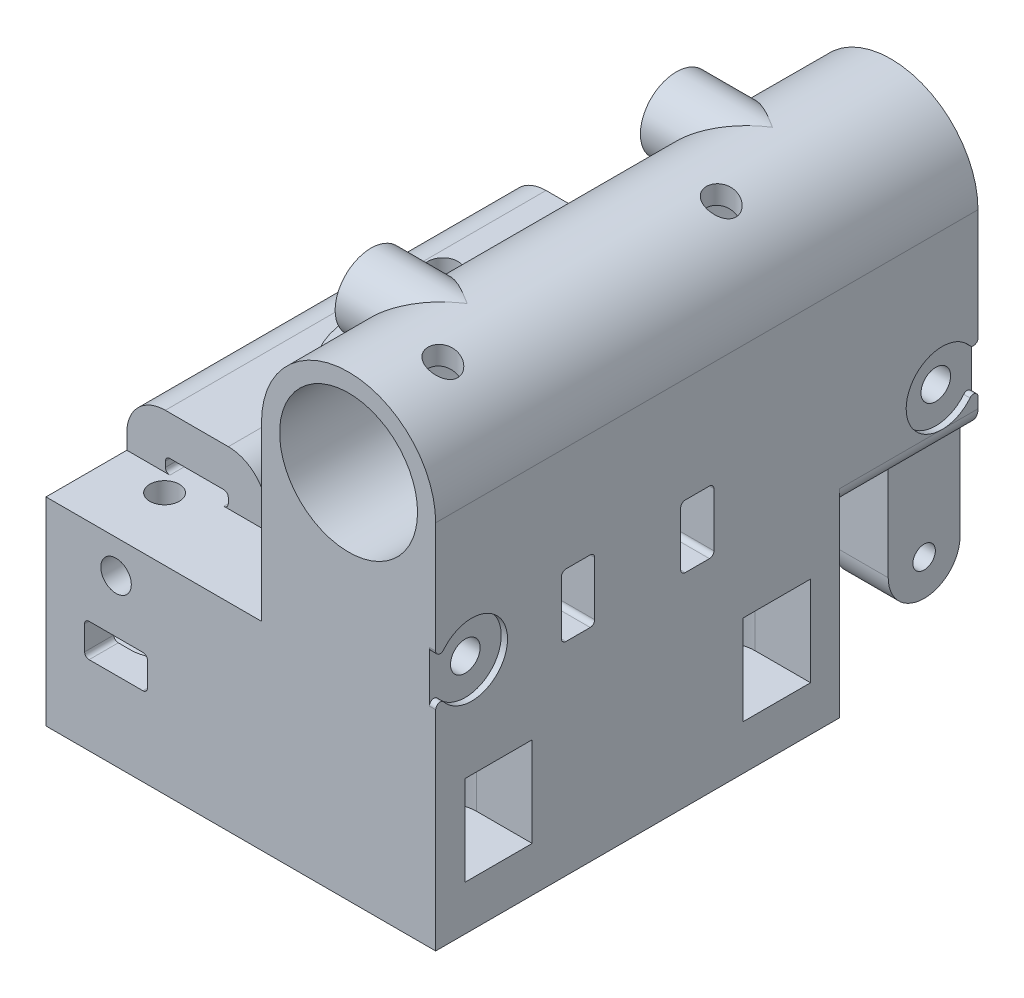
SolidWorks part; units mm, degrees
ref_plane "Front Plane" through (0, 0, 0) normal (0, 0, 1) x (1, 0, 0)
ref_plane "Top Plane" through (0, 0, 0) normal (0, 1, 0) x (1, 0, 0)
ref_plane "Right Plane" through (0, 0, 0) normal (1, 0, 0) x (0, 0, -1)
sketch "Sketch1" plane through (0, 0, 0) normal (0, 0, 1) x (1, 0, 0)
  line L57 (9.7, 0) -> (9.7, -41.3)
  line L58 (-9.7, -19.2) -> (-18.1, -19.2)
  line L61 (-29.4, -32) -> (-29.4, -29.3)
  line L62 (-29.4, -18.1) -> (-29.4, -18.7)
  line L63 (-28.9, -19.2) -> (-22.9, -19.2)
  line L64 (-22.4, -18.7) -> (-22.4, -18.1)
  line L65 (-22.9, -17.6) -> (-28.9, -17.6)
  line L66 (-28.9, -32.5) -> (-22.9, -32.5)
  line L67 (-22.4, -32) -> (-22.4, -29.3)
  line L68 (-28.9, -28.8) -> (-22.9, -28.8)
  line L76 (-9.7, -19.2) -> (-9.7, 0)
  line L77 (9.7, -41.3) -> (-33.7, -41.3)
  line L80 (-33.7, -41.3) -> (-33.7, -17.49)
  line L81 (-29.41, -13.2) -> (-22.39, -13.2)
  line L82 (-18.1, -17.49) -> (-18.1, -19.2)
  circle A0 centre (0, 0) radius 7.68
  arc A39 (9.7, 0) -> (-9.7, 0) centre (0, 0) ccw
  circle A59 centre (-25.9, -22.91) radius 1.7
  arc A60 (-28.9, -17.6) -> (-29.4, -18.1) centre (-28.9, -18.1) ccw
  arc A61 (-29.4, -18.7) -> (-28.9, -19.2) centre (-28.9, -18.7) ccw
  arc A62 (-22.9, -19.2) -> (-22.4, -18.7) centre (-22.9, -18.7) ccw
  arc A63 (-22.4, -18.1) -> (-22.9, -17.6) centre (-22.9, -18.1) ccw
  arc A64 (-29.4, -29.3) -> (-28.9, -28.8) centre (-28.9, -29.3) cw
  arc A65 (-22.4, -29.3) -> (-22.9, -28.8) centre (-22.9, -29.3) ccw
  arc A66 (-22.9, -32.5) -> (-22.4, -32) centre (-22.9, -32) ccw
  arc A67 (-29.4, -32) -> (-28.9, -32.5) centre (-28.9, -32) ccw
  arc A70 (-29.41, -13.2) -> (-33.7, -17.49) centre (-29.41, -17.49) ccw
  arc A71 (-18.1, -17.49) -> (-22.39, -13.2) centre (-22.39, -17.49) ccw
extrude "Boss-Extrude1" add sketch "Sketch1" along normal blind 60.4
sketch "Sketch8" plane through (0, -41.3, 0) normal (0, 1, 0) x (1, 0, 0)
  line L6 (-12, -48.01) -> (-7.68, -48.01)
  line L8 (-12, -27.79) -> (-7.68, -27.79)
  line L9 (-7.68, -48.01) -> (-7.68, -27.79)
  arc A1 (-12, -27.79) -> (-12, -48.01) centre (-12, -37.9) ccw
extrude "Boss-Extrude3" add sketch "Sketch8" along normal blind 34.02
sketch "Sketch2" plane through (0, 0, 0) normal (0, 0, -1) x (-1, 0, 0)
  line L0 (22.39, -15.34) -> (29.41, -15.34)
  line L1 (20.24, -17.49) -> (20.24, -24.62)
  line L2 (22.39, -26.77) -> (29.41, -26.77)
  line L3 (31.56, -17.49) -> (31.56, -24.62)
  arc A1 (22.39, -15.34) -> (20.24, -17.49) centre (22.39, -17.49) ccw
  arc A2 (31.56, -17.49) -> (29.41, -15.34) centre (29.41, -17.49) ccw
  arc A3 (29.41, -26.77) -> (31.56, -24.62) centre (29.41, -24.62) ccw
  arc A4 (20.24, -24.62) -> (22.39, -26.77) centre (22.39, -24.62) ccw
sketch "Sketch3" plane through (9.7, 0, 0) normal (1, 0, 0) x (0, 0, -1)
  line L11 (-46.39, -12.2) -> (-46.39, -18.2)
  line L12 (-43.19, -18.7) -> (-45.89, -18.7)
  line L13 (-42.69, -12.2) -> (-42.69, -18.2)
  line L14 (-43.19, -11.7) -> (-45.89, -11.7)
  line L15 (-33.11, -12.2) -> (-33.11, -18.2)
  line L16 (-29.91, -18.7) -> (-32.61, -18.7)
  line L17 (-29.41, -12.2) -> (-29.41, -18.2)
  line L18 (-29.91, -11.7) -> (-32.61, -11.7)
  circle A10 centre (-4, -15.2) radius 1.65
  circle A11 centre (-56.4, -15.2) radius 1.65
  arc A12 (-29.91, -11.7) -> (-29.41, -12.2) centre (-29.91, -12.2) cw
  arc A13 (-29.41, -18.2) -> (-29.91, -18.7) centre (-29.91, -18.2) cw
  arc A14 (-32.61, -18.7) -> (-33.11, -18.2) centre (-32.61, -18.2) cw
  arc A15 (-32.61, -11.7) -> (-33.11, -12.2) centre (-32.61, -12.2) ccw
  arc A16 (-43.19, -11.7) -> (-42.69, -12.2) centre (-43.19, -12.2) cw
  arc A17 (-42.69, -18.2) -> (-43.19, -18.7) centre (-43.19, -18.2) cw
  arc A18 (-45.89, -18.7) -> (-46.39, -18.2) centre (-45.89, -18.2) cw
  arc A19 (-45.89, -11.7) -> (-46.39, -12.2) centre (-45.89, -12.2) ccw
sketch "Sketch4" plane through (0, -41.3, 0) normal (0, -1, 0) x (1, 0, 0)
  circle A0 centre (-12, 37.9) radius 8.49
extrude "Cut-Extrude1" cut sketch "Sketch4" against normal blind 32
sketch "Sketch6" plane through (0, -41.3, 0) normal (0, -1, 0) x (1, 0, 0)
  circle A1 centre (3.5, 53.4) radius 1.65
  circle A2 centre (-27.5, 53.4) radius 1.65
  circle A3 centre (-27.5, 22.4) radius 1.65
  circle A4 centre (3.5, 22.4) radius 1.65
extrude "Cut-Extrude2" cut sketch "Sketch2" against normal blind 30.2
extrude "Cut-Extrude4" cut sketch "Sketch3" against normal up to next
sketch "Sketch9" plane through (9.7, 0, 0) normal (1, 0, 0) x (0, 0, -1)
  line L0 (-60.4, -12.3716) -> (-60.4, -18.0284)
  line L1 (0, -12.3716) -> (0, -18.0284)
  arc A0 (-60.4, -12.3716) -> (-59.5111, -12.6858) centre (-59.9, -12.3716) ccw
  arc A1 (-59.5111, -17.7142) -> (-59.5111, -12.6858) centre (-56.4, -15.2) ccw
  arc A2 (-59.5111, -17.7142) -> (-60.4, -18.0284) centre (-59.9, -18.0284) ccw
  arc A3 (-0.8889, -17.7142) -> (0, -18.0284) centre (-0.5, -18.0284) cw
  arc A4 (-0.8889, -17.7142) -> (-0.8889, -12.6858) centre (-4, -15.2) cw
  arc A5 (0, -12.3716) -> (-0.8889, -12.6858) centre (-0.5, -12.3716) cw
extrude "Cut-Extrude5" cut sketch "Sketch9" against normal blind 0.7
sketch "Sketch10" plane through (-9.7, 0, 0) normal (-1, 0, 0) x (0, 0, 1)
  circle A0 centre (4, -15.2) radius 3.6
  circle A1 centre (56.4, -15.2) radius 3.6
extrude "Cut-Extrude6" cut sketch "Sketch10" against normal blind 2
sketch "Sketch14" plane through (0, 0, 0) normal (0, 0, -1) x (-1, 0, 0)
  line L3 (-9.7, -19.2) -> (-9.7, -41.3)
  line L5 (-7.7, -21.2) -> (7.7, -21.2)
  line L8 (9.7, -19.2) -> (18.1, -19.2)
  line L11 (18.1, -19.2) -> (18.1, -24.62)
  line L12 (-9.7, -41.3) -> (33.7, -41.3)
  line L15 (33.7, -41.3) -> (33.7, -24.62)
  line L17 (22.39, -28.91) -> (29.41, -28.91)
  arc A2 (-9.7, -19.2) -> (-7.7, -21.2) centre (-7.7, -19.2) ccw
  arc A3 (7.7, -21.2) -> (9.7, -19.2) centre (7.7, -19.2) ccw
  arc A8 (18.1, -24.62) -> (22.39, -28.91) centre (22.39, -24.62) ccw
  arc A9 (29.41, -28.91) -> (33.7, -24.62) centre (29.41, -24.62) ccw
sketch "Sketch15" plane through (0, 0, 0) normal (0, 0, -1) x (-1, 0, 0)
  line L1 (22.39, -13.2) -> (29.41, -13.2)
  line L3 (22.39, -28.91) -> (29.41, -28.91)
  line L12 (18.1, -17.49) -> (18.1, -24.62)
  line L14 (33.7, -17.49) -> (33.7, -24.62)
  arc A4 (22.39, -13.2) -> (18.1, -17.49) centre (22.39, -17.49) ccw
  arc A5 (33.7, -17.49) -> (29.41, -13.2) centre (29.41, -17.49) ccw
  arc A9 (29.41, -28.91) -> (33.7, -24.62) centre (29.41, -24.62) ccw
  arc A10 (18.1, -24.62) -> (22.39, -28.91) centre (22.39, -24.62) ccw
extrude "Cut-Extrude8" cut sketch "Sketch14" against normal blind 15.4
extrude "Cut-Extrude9" cut sketch "Sketch15" against normal blind 9
extrude "Cut-Extrude10" cut sketch "Sketch6" against normal through all
sketch "Sketch16" plane through (0, -41.3, 0) normal (0, -1, 0) x (1, 0, 0)
  circle A0 centre (-12, 37.9) radius 11.5
extrude "Cut-Extrude11" cut sketch "Sketch16" against normal blind 2.5
sketch "Sketch17" plane through (0, 0, 60.4) normal (0, 0, 1) x (1, 0, 0)
  line L3 (-29.41, -13.2) -> (-22.39, -13.2)
  line L6 (-33.7, -17.49) -> (-33.7, -19.2)
  line L7 (-33.7, -19.2) -> (-18.1, -19.2)
  line L8 (-18.1, -17.49) -> (-18.1, -19.2)
  arc A5 (-18.1, -17.49) -> (-22.39, -13.2) centre (-22.39, -17.49) ccw
  arc A6 (-29.41, -13.2) -> (-33.7, -17.49) centre (-29.41, -17.49) ccw
extrude "Cut-Extrude12" cut sketch "Sketch17" against normal blind 9
sketch "Sketch12" plane through (0, -41.3, 0) normal (0, -1, 0) x (1, 0, 0)
  line L5 (-27.5, 49.65) -> (-35.18, 49.65)
  line L19 (-27.5, 57.15) -> (-35.18, 57.15)
  line L20 (-35.18, 49.65) -> (-35.18, 57.15)
  line L21 (3.5, 49.65) -> (9.7, 49.65)
  line L23 (3.5, 57.15) -> (9.7, 57.15)
  line L24 (9.7, 49.65) -> (9.7, 57.15)
  line L25 (3.5, 18.65) -> (9.7, 18.65)
  line L27 (3.5, 26.15) -> (9.7, 26.15)
  line L28 (9.7, 18.65) -> (9.7, 26.15)
  circle A5 centre (-27.5, 22.4) radius 3.75
  arc A6 (-27.5, 49.65) -> (-27.5, 57.15) centre (-27.5, 53.4) ccw
  arc A7 (3.5, 57.15) -> (3.5, 49.65) centre (3.5, 53.4) ccw
  arc A8 (3.5, 26.15) -> (3.5, 18.65) centre (3.5, 22.4) ccw
extrude "Cut-Extrude13" cut sketch "Sketch12" against normal blind 10 from offset 5 offset against normal yes
sketch "Sketch20" plane through (-9.7, 0, 0) normal (-1, 0, 0) x (0, 0, 1)
  circle A0 centre (13.2, 5.7) radius 4
  circle A1 centre (47.2, 5.7) radius 4
extrude "Boss-Extrude4" add sketch "Sketch20" against normal up to surface and the other way blind 1 up to face at (3.0891, 9.195, 23.998)
sketch "Sketch19" plane through (-10.7, 0, 0) normal (-1, 0, 0) x (0, 0, 1)
  circle A0 centre (13.2, 5.7) radius 1.65
  circle A1 centre (47.2, 5.7) radius 1.65
extrude "Cut-Extrude14" cut sketch "Sketch19" against normal up to next
sketch "Sketch21" plane through (9.7, 0, 0) normal (1, 0, 0) x (0, 0, -1)
  line L7 (-8, -32.5) -> (-8, -21.2)
  line L8 (-8, -21.2) -> (0, -21.2)
  line L9 (0, -32.5) -> (0, -21.2)
  circle A0 centre (-4, -32.5) radius 1.25
  arc A1 (-8, -32.5) -> (0, -32.5) centre (-4, -32.5) ccw
extrude "Boss-Extrude5" add sketch "Sketch21" against normal blind 6 from vertex starting at point (7.7, -21.2, 0)
sketch "Sketch22" plane through (0, 0, 30.2) normal (0, 0, -1) x (-1, 0, 0)
  line L0 (22.9, -16.9) -> (28.9, -16.9)
  line L1 (22.4, -17.4) -> (22.4, -18.7)
  line L2 (22.9, -19.2) -> (28.9, -19.2)
  line L3 (29.4, -17.4) -> (29.4, -18.7)
  arc A0 (28.9, -19.2) -> (29.4, -18.7) centre (28.9, -18.7) ccw
  arc A1 (29.4, -17.4) -> (28.9, -16.9) centre (28.9, -17.4) ccw
  arc A2 (22.9, -16.9) -> (22.4, -17.4) centre (22.9, -17.4) ccw
  arc A3 (22.9, -19.2) -> (22.4, -18.7) centre (22.9, -18.7) cw
extrude "Cut-Extrude15" cut sketch "Sketch22" against normal blind 8
